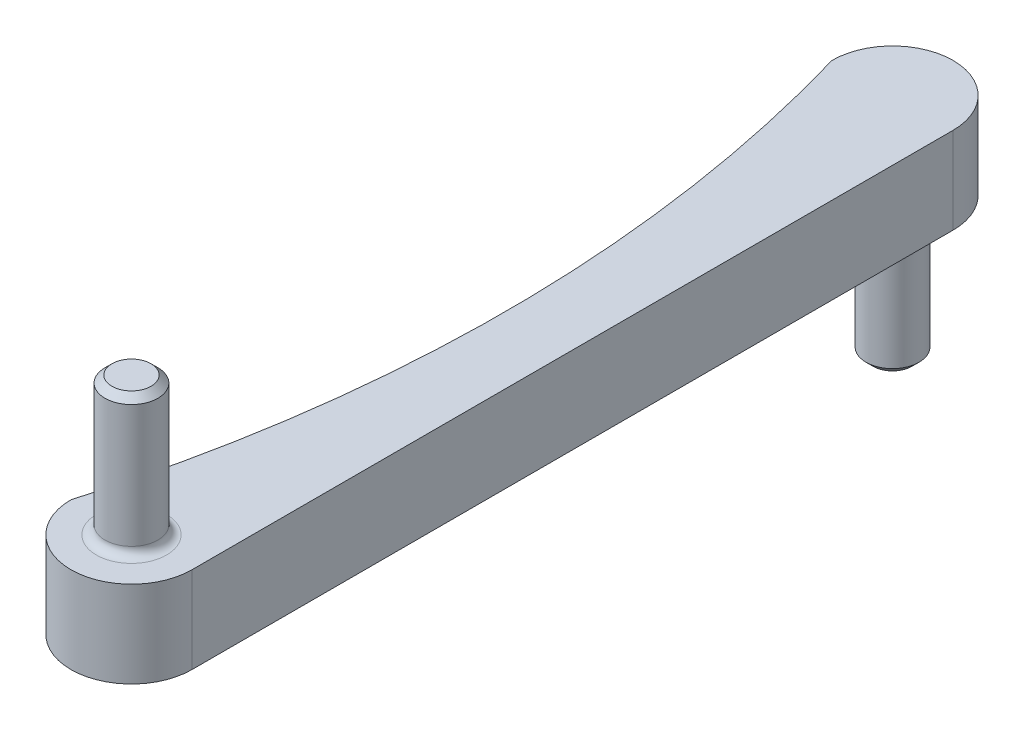
SolidWorks part; units mm, degrees
material "PLA2"
ref_plane "Front Plane" through (0, 0, 0) normal (0, 0, 1) x (1, 0, 0)
ref_plane "Top Plane" through (0, 0, 0) normal (0, 1, 0) x (1, 0, 0)
ref_plane "Right Plane" through (0, 0, 0) normal (1, 0, 0) x (0, 0, -1)
sketch "Sketch1" plane through (0, 0, 0) normal (0, 1, 0) x (1, 0, 0)
  line L0 (0, 0) -> (0, 55.88) construction
  line L3 (-4.445, 0) -> (-4.445, 55.88)
  line L4 (4.445, 0) -> (4.445, 55.88)
  arc A4 (-4.445, 0) -> (4.445, 0) centre (0, 0) ccw
  arc A5 (4.445, 55.88) -> (-4.445, 55.88) centre (0, 55.88) ccw
  point P3 (0, 27.94)
  dimension "D1" = 8.89
  dimension "D2" = 55.88
extrude "Boss-Extrude1" add sketch "Sketch1" along normal blind 6.35
sketch "Sketch3" plane through (0, 6.35, 0) normal (0, 1, 0) x (1, 0, 0)
  circle A0 centre (0, 0) radius 1.9431
  dimension "D1" = 3.8862
extrude "Boss-Extrude3" add sketch "Sketch3" along normal blind 10.16
sketch "Sketch4" plane through (0, 0, 0) normal (0, -1, 0) x (1, 0, 0)
  circle A0 centre (0, -55.88) radius 1.9431
  dimension "D1" = 3.8862
extrude "Boss-Extrude4" add sketch "Sketch4" along normal blind 10.16
sketch "Sketch5" plane through (0, 6.35, 0) normal (0, 1, 0) x (1, 0, 0)
  line L0 (0, 59.055) -> (0, 0) construction
  line L1 (-4.445, 55.88) -> (-4.445, 0)
  arc A2 (-4.445, 55.88) -> (-4.445, 0) centre (-100.4209, 27.94) cw
  dimension "D1" = 99.96
extrude "Cut-Extrude1" cut sketch "Sketch5" against normal through all
sketch "Sketch6" plane through (0, 0, 0) normal (0, -1, 0) x (1, 0, 0)
  circle A0 centre (0, -59.055) radius 3.475
  dimension "D1" = 6.95
extrude "Boss-Extrude5" [suppressed] add sketch "Sketch6" along normal blind 2.032
sketch "Sketch7" plane through (0, 6.35, 0) normal (0, 1, 0) x (1, 0, 0)
  circle A0 centre (0, 0) radius 2.77
  dimension "D1" = 5.54
extrude "Boss-Extrude6" [suppressed] add sketch "Sketch7" along normal up to vertex
chamfer "Chamfer1" [suppressed] distance 0.508 angle 45
chamfer "Chamfer3" [suppressed] distance 0.508 angle 45
fillet "Fillet1" [suppressed] radius 0.381
fillet "Fillet2" radius 0.635 2 edges at (0, 0, -53.9369) (0, 6.35, 1.9431)
chamfer "Chamfer4" distance 0.508 angle 45 2 edges at (0, 16.51, 1.9431) (0, -10.16, -57.8231)
